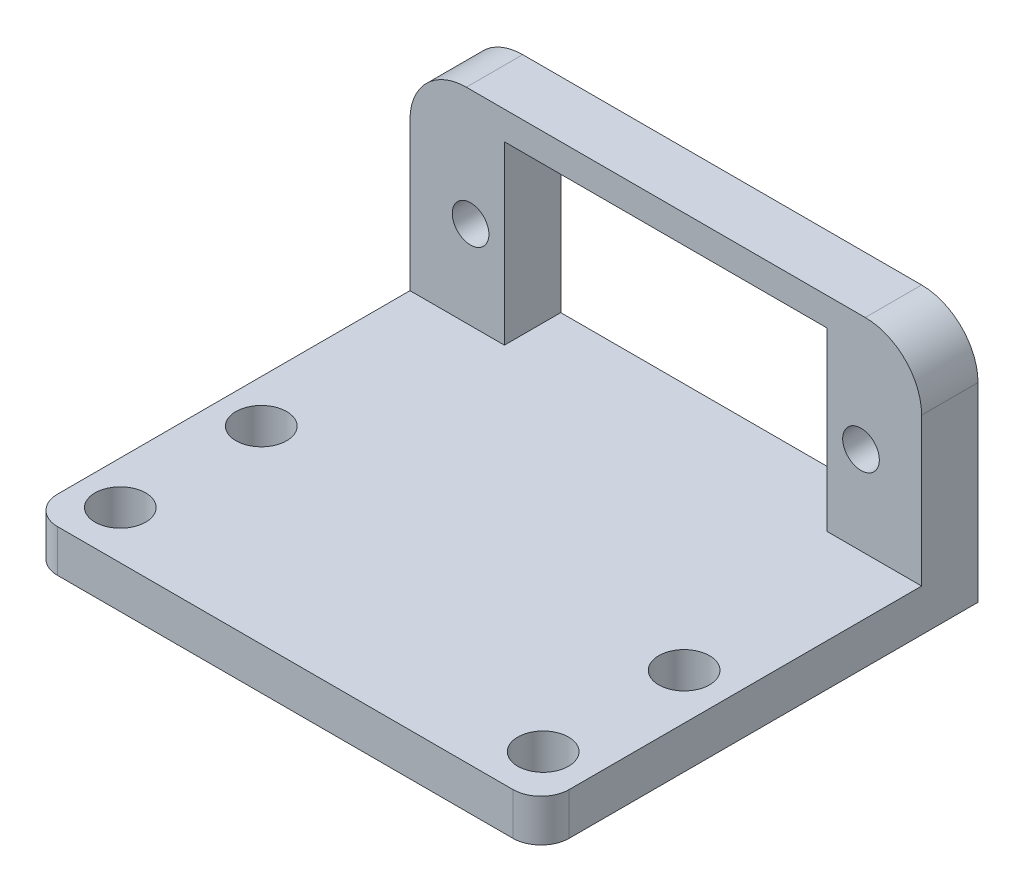
SolidWorks part; units mm, degrees
ref_plane "Front Plane" through (0, 0, 0) normal (0, 0, 1) x (1, 0, 0)
ref_plane "Top Plane" through (0, 0, 0) normal (0, 1, 0) x (1, 0, 0)
ref_plane "Right Plane" through (0, 0, 0) normal (1, 0, 0) x (0, 0, -1)
sketch "Sketch1" plane through (0, 0, 0) normal (0, 0, 1) x (1, 0, 0)
  line L1 (1.5, 2.7805) -> (1.5, 14.8805) construction
  line L2 (-0.5, 8.8305) -> (35.8, 8.8305) construction
  line L3 (-0.5, 17.0805) -> (35.8, 17.0805)
  line L4 (-0.5, 17.0805) -> (-0.5, 0.5805)
  line L5 (-0.5, 0.5805) -> (35.8, 0.5805)
  line L6 (35.8, 17.0805) -> (35.8, 0.5805)
  line L7 (1.5, 14.8805) -> (33.8, 14.8805) construction
  line L8 (17.65, 14.8805) -> (17.65, 8.8305) construction
  line L9 (6.4, 14.8805) -> (6.4, 2.7805) construction
  line L11 (6.2, 15.0805) -> (29.1, 15.0805)
  line L12 (6.2, 15.0805) -> (6.2, 2.5805)
  line L13 (6.2, 2.5805) -> (29.1, 2.5805)
  line L14 (29.1, 15.0805) -> (29.1, 2.5805)
  point P1 (0, 0)
  point P10 (1.5, 8.8305)
  point P21 (17.65, 15.0805)
  point P22 (6.2, 8.8305)
  point P23 (0, 0)
  point P25 (6.4, 20.2221)
  point P27 (6.4, 8.1221)
  point P29 (1.5, 20.2221)
  point P31 (1.5, 16.6611)
  point P33 (0, 0)
  point P34 (1.5, 14.8805)
  point P36 (0, 0)
  point P37 (0, 0)
  point P38 (33.8, 14.8805)
  point P40 (17.65, 7.5255)
  point P41 (1.5, 2.7805)
  dimension "D1" = 2
  dimension "D2" = 2.2
  dimension "D3" = 0.2
  dimension "D4" = 0.2
extrude "Boss-Extrude1" add sketch "Sketch1" along normal blind 4
fillet "Fillet1" radius 4 2 edges at (35.8, 17.0805, 2) (-0.5, 17.0805, 2)
sketch "Sketch2" plane through (0, 0, 4) normal (0, 0, 1) x (1, 0, 0)
  point P0 (31.5, 8.8305)
  point P3 (3.8, 8.8305)
hole_wizard "M2 Clearance Hole1" positions "Sketch2" profile "Sketch3" hole size "M2" standard "ANSI Metric" end condition through all
sketch "Sketch3" plane through (31.5, 8.8305, 4) normal (1, 0, 0) x (0, -1, 0)
  line L0 (0, 0) -> (0, 4)
  line L1 (0, 4) -> (1.3, 4)
  line L2 (1.3, 4) -> (1.3, 0)
  line L5 (1.3, 0) -> (0, 0)
  line L11 (0, -6.35) -> (0, 107.95) construction
  dimension "Thru Hole Dia." = 2.6
  dimension "Thru Hole Depth" = 4
sketch "Sketch4" plane through (0, 0, 4) normal (0, 0, 1) x (1, 0, 0)
  line L0 (-0.5, 13.0805) -> (-0.5, 0.5805) construction
  line L1 (-0.5, 2.5805) -> (35.8, 2.5805)
  line L2 (-0.5, 2.5805) -> (-0.5, -0.4195)
  line L3 (-0.5, -0.4195) -> (35.8, -0.4195)
  line L4 (35.8, 2.5805) -> (35.8, -0.4195)
  line L5 (6.2, 2.5805) -> (29.1, 2.5805) construction
  line L6 (35.8, 0.5805) -> (35.8, 13.0805) construction
  dimension "D1" = 3
extrude "Boss-Extrude2" add sketch "Sketch4" along normal blind 27
extrude "Boss-Extrude3" add sketch "Sketch4<2>" against normal up to surface (4 mm away) up to face at (32.8, 8.8305, 0)
sketch "Sketch4<2>" plane through (0, 0, 4) normal (0, 0, 1) x (1, 0, 0) same geometry as "Sketch4"
fillet "Fillet2" radius 2 2 edges at (35.8, 1.0805, 31) (-0.5, 1.0805, 31)
sketch "Sketch5" plane through (0, 2.5805, 0) normal (0, 1, 0) x (1, 0, 0)
  point P0 (2.55, -17.6)
  point P3 (2.55, -27.6)
  point P6 (32.55, -17.6)
  point P9 (32.55, -27.6)
hole_wizard "M3 Clearance Hole1" positions "Sketch5" profile "Sketch6" hole size "M3" standard "ANSI Metric" end condition through all
sketch "Sketch6" plane through (2.55, 2.5805, 17.6) normal (1, 0, 0) x (0, 0, 1)
  line L0 (0, 0) -> (0, 3)
  line L1 (0, 3) -> (1.8, 3)
  line L2 (1.8, 3) -> (1.8, 0)
  line L5 (1.8, 0) -> (0, 0)
  line L11 (0, -6.35) -> (0, 107.95) construction
  dimension "Thru Hole Dia." = 3.6
  dimension "Thru Hole Depth" = 3
